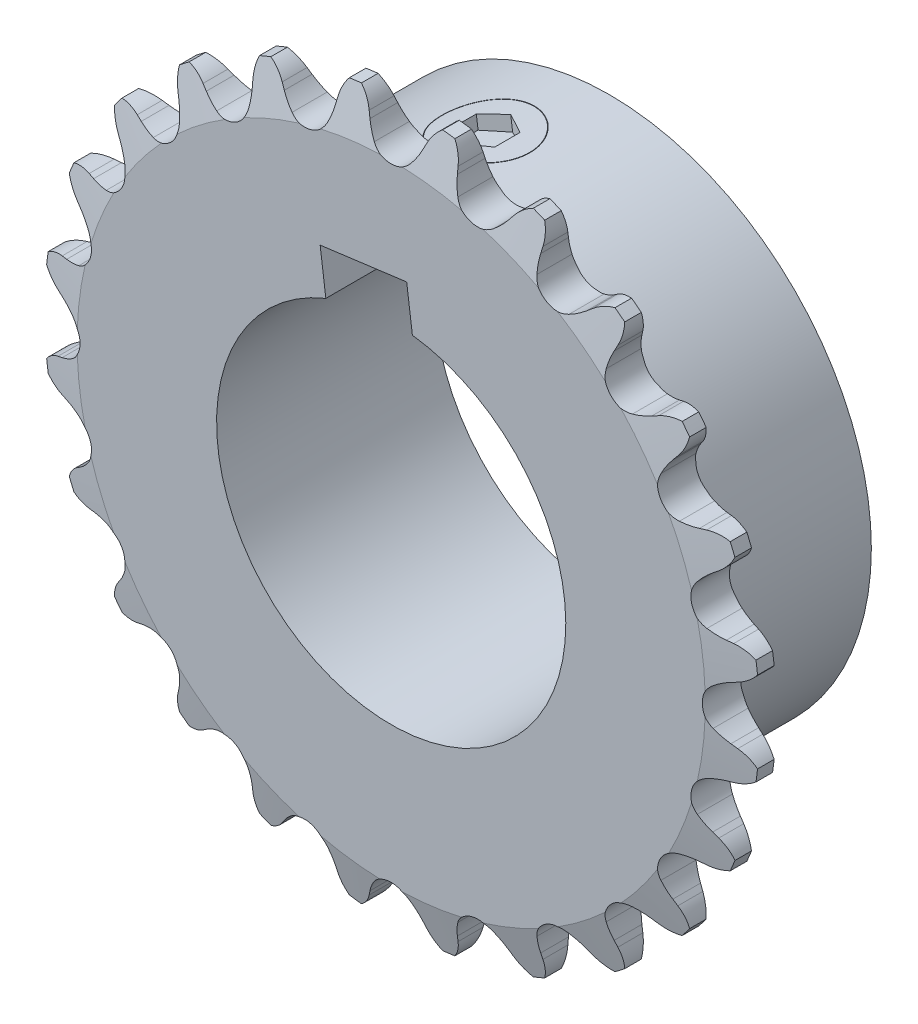
SolidWorks part; units mm, degrees
note: '?' marks a value the reader was unsure of.
ref_plane "Front Plane" through (0, 0, 0) normal (0, 0, 1) x (1, 0, 0)
ref_plane "Top Plane" through (0, 0, 0) normal (0, 1, 0) x (1, 0, 0)
ref_plane "Right Plane" through (0, 0, 0) normal (1, 0, 0) x (0, 0, -1)
ref_axis "Axis1" through (0, 0, -88.99) along (0, 0, 1)?
sketch "Sprocket-BaseSketch" plane through (0, 0, 0) normal (1, 0, 0) x (0, 0, -1)
  line L0 (1.397, 0) -> (1.397, 22.8465)
  line L1 (1.397, 22.8465) -> (0.6032, 26.0215)
  line L2 (0.6032, 26.0215) -> (-0.6032, 26.0215)
  line L3 (-0.6032, 26.0215) -> (-1.397, 22.8465)
  line L4 (-1.397, 22.8465) -> (-1.397, 0)
  line L5 (-1.397, 0) -> (1.397, 0)
  line L6 (5.588, 0) -> (-1.7463, 0) construction
  dimension "Hub Surface" = 1.397
  dimension "RightSide (1)" = 0.7938
  dimension "RightSide (2)" = 3.175
  dimension "OD" = 26.0215
  dimension "LeftSide (1)" = 0.7938
  dimension "LeftSide (2)" = 3.175
  dimension "Tooth Width" = 2.794
revolve "25 (04C) ANSI (ISO) Chain Number, 1.915in P.D." add sketch "Sprocket-BaseSketch" angle 360 about L6
sketch "Tooth-Sketch" plane through (0, 0, 0) normal (0, 0, 1) x (1, 0, 0)
  line L0 (0, 0) -> (0, 32.4328) construction
  line L1 (1.932, 24.319) -> (2.0923, 24.7192)
  line L2 (-1.932, 24.319) -> (-2.0923, 24.7192)
  line L3 (0, 24.3246) -> (6.2957, 23.4958) construction
  line L4 (0, 24.3246) -> (-6.2957, 23.4958) construction
  arc A0 (-1.3466, 23.2913) -> (1.3466, 23.2913) centre (0, 24.3246) ccw
  arc A1 (1.3466, 23.2913) -> (1.932, 24.319) centre (-2.0957, 25.9327) ccw
  arc A2 (-1.3466, 23.2913) -> (-1.932, 24.319) centre (2.0957, 25.9327) cw
  arc A3 (2.0923, 24.7192) -> (4.5833, 26.4046) centre (4.5833, 23.7212) cw
  arc A4 (-2.0923, 24.7192) -> (-4.5833, 26.4046) centre (-4.5833, 23.7212) ccw
  arc A5 (4.5833, 26.4046) -> (-4.5833, 26.4046) centre (0, 0) ccw
extrude "Tooth-Cut, Number of teeth: 24" cut sketch "Tooth-Sketch" against normal through all and the other way through all
pattern_circular "Tooth Pattern, 24 / 24" count 24 every 15 about axis through (0, 0, 0) along (0, 0, 1) of "Tooth-Cut, Number of teeth: 24"
sketch "Sketch3" plane through (0, 0, 0) normal (1, 0, 0) x (0, 0, -1)
  line L0 (-13.081, 0) -> (13.081, 0) construction
  line L1 (1.397, 0) -> (1.397, 19.05)
  line L2 (1.397, 19.05) -> (14.478, 19.05)
  line L3 (14.478, 19.05) -> (14.478, 0)
  line L4 (14.478, 0) -> (1.397, 0)
  dimension "Hub Mounting" = 1.397
  dimension "Hub OD" = 19.05
  dimension "Hub Width" = 13.081
revolve "Hub-Revolve1" add sketch "Sketch3" angle 360 about L0
sketch "Sketch4" plane through (0, 0, -14.478) normal (0, 0, -1) x (-1, 0, 0)
  circle A0 centre (0, 0) radius 12.7
  dimension "Bore Diameter " = 25.4
extrude "Cut-Extrude1" cut sketch "Sketch4" against normal through all
sketch "Sketch5" plane through (0, 0, 0) normal (1, 0, 0) x (0, 0, -1)
  line L0 (14.478, 0) -> (-1.397, 0) construction
  line L1 (14.478, -19.05) -> (14.478, 19.05) construction
  line L2 (-1.397, 0.8085) -> (-1.397, -0.8085) construction
ref_plane "Plane1" through (0, 0, 0) normal (-0.1305, 0.9914, 0) x (-0.9914, -0.1305, 0)
sketch "Sketch6" plane through (0, 0, -14.478) normal (0, 0, -1) x (-1, 0, 0)
  line L0 (-1.5428, 12.6059) -> (-1.1284, 15.7538)
  line L1 (-1.1284, 15.7538) -> (5.1673, 14.9249)
  line L2 (5.1673, 14.9249) -> (4.7529, 11.7771)
  line L3 (4.7529, 11.7771) -> (-1.5428, 12.6059)
  line L4 (8.6566, -1.1397) -> (-8.6566, 1.1397) construction
  circle A0 centre (0, 0) radius 12.7 construction
  dimension "Keyway Wd " = 6.35
  dimension "Keyway Dp " = 3.175
extrude "Cut-Extrude2" cut sketch "Sketch6" against normal through all
sketch "Sketch7" plane through (-2.0195, 15.3394, 0) normal (0.1305, -0.9914, 0) x (0.9914, 0.1305, 0)
  line L0 (0, -14.478) -> (0, -1.397) construction
  line L1 (-2.1786, -1.397) -> (2.1786, -1.397) construction
  line L2 (-3.175, 1.397) -> (-3.175, -14.478) construction
  circle A0 centre (0, -7.9375) radius 3.175
extrude "Cut-Extrude3" cut sketch "Sketch7" against normal through all draft 1 draft outward yes
sketch "Sketch8" plane through (-2.0195, 15.3394, 0) normal (0.1305, -0.9914, 0) x (0.9914, 0.1305, 0)
  line L0 (-3.175, -7.9375) -> (-3.2326, -7.9375) construction
  line L1 (-3.175, 1.397) -> (-3.175, -14.478) construction
  line L2 (-3.2038, -7.9375) -> (-3.2038, -14.478) construction
  line L3 (-19.05, -14.478) -> (19.05, -14.478) construction
  circle A0 centre (0, -7.9375) radius 3.2038
  arc A1 (-3.175, -7.9375) -> (3.175, -7.9375) centre (0, -7.9375) ccw construction
  spline S0 degree 3 poles (-2.797, -9.5747) (-2.5581, -9.9284) (-2.4233, -10.0905) (-2.1245, -10.3867) (-1.9584, -10.522) (-1.6051, -10.7557) (-1.419, -10.8541) (-1.0278, -11.0143) (-0.8212, -11.0759) (-0.4063, -11.1563) (-0.1961, -11.176) (0.23, -11.1738) (0.4428, -11.1514) (0.8561, -11.0665) (1.06, -11.0034) (1.4521, -10.8378) (1.6372, -10.737) (1.9863, -10.5004) (2.1516, -10.3629) (2.4479, -10.0625) (2.5804, -9.8991) (2.8137, -9.5454) (2.9136, -9.3558) (3.0726, -8.9655) (3.1331, -8.7629) (3.2143, -8.3428) (3.2337, -8.1321) (3.2315, -7.7099) (3.2094, -7.4959) (3.1244, -7.08) (3.0621, -6.8785) (2.8984, -6.4883) (2.7961, -6.2991) (2.5603, -5.9498) (2.4262, -5.7875) (2.1243, -5.4879) (1.9595, -5.354) (1.6087, -5.1215) (1.4201, -5.0214) (1.0266, -4.8603) (0.8245, -4.8) (0.4097, -4.7192) (0.1948, -4.699) (-0.2287, -4.7012) (-0.4387, -4.7229) (-0.855, -4.8081) (-1.0599, -4.8717) (-1.4484, -5.0355) (-1.6349, -5.1365) (-1.9876, -5.3754) (-2.1495, -5.5102) (-2.4455, -5.8097) (-2.5808, -5.9765) (-2.8136, -6.3294) (-2.9119, -6.5156) (-3.0719, -6.9074) (-3.1334, -7.1139) (-3.2136, -7.5284) (-3.2336, -7.7388) (-3.2316, -8.1658) (-3.2096, -8.3776) (-3.1254, -8.7911) (-3.0625, -8.9956) (-2.8978, -9.3881) (-2.797, -9.5747) (-2.5581, -9.9284) (-2.4233, -10.0905) knots -0.03125 -0.03125 0 0 0.03125 0.03125 0.0625 0.0625 0.09375 0.09375 0.125 0.125 0.15625 0.15625 0.1875 0.1875 0.21875 0.21875 0.25 0.25 0.28125 0.28125 0.3125 0.3125 0.34375 0.34375 0.375 0.375 0.40625 0.40625 0.4375 0.4375 0.46875 0.46875 0.5 0.5 0.53125 0.53125 0.5625 0.5625 0.59375 0.59375 0.625 0.625 0.65625 0.65625 0.6875 0.6875 0.71875 0.71875 0.75 0.75 0.78125 0.78125 0.8125 0.8125 0.84375 0.84375 0.875 0.875 0.90625 0.90625 0.9375 0.9375 0.96875 0.96875 1 1 1.03125 1.03125 1.0625 only from (-2.6775, -9.7515) to (-2.6775, -9.7515) construction
extrude "Extrude1" add sketch "Sketch8" against normal up to surface (3.3069 mm away)
sketch "Sketch9" plane through (-2.0195, 15.3394, 0) normal (0.1305, -0.9914, 0) x (0.9914, 0.1305, 0)
  line L0 (0, -7.9375) -> (3.2038, -7.9375) construction
  line L1 (1.6019, -7.9375) -> (1.6019, -10.7121) construction
  line L3 (0, -9.7872) -> (1.6019, -8.8624)
  line L4 (1.6019, -8.8624) -> (1.6019, -7.0126)
  line L5 (1.6019, -7.0126) -> (0, -6.0878)
  line L6 (0, -6.0878) -> (-1.6019, -7.0126)
  line L7 (-1.6019, -7.0126) -> (-1.6019, -8.8624)
  line L8 (-1.6019, -8.8624) -> (0, -9.7872)
  circle A0 centre (0, -7.9375) radius 3.2038 construction
  circle A1 centre (0, -7.9375) radius 1.6019 construction
extrude "Cut-Extrude4" cut sketch "Sketch9" against normal through all from offset 2.54
sketch "Sketch10" plane through (0, 0, -14.478) normal (0, 0, -1) x (-1, 0, 0)
  line L0 (-25.7989, 3.3965) -> (25.7989, -3.3965)
  line L1 (-6.2957, -23.4958) -> (0, -24.3246)
  line L2 (8.6566, -1.1397) -> (-8.6566, 1.1397) construction
  line L3 (-26.0277, 1.6589) -> (25.5701, -5.1341)
  line L4 (-6.0669, -21.7582) -> (0.2288, -22.587)
  circle A0 centre (0, 0) radius 26.0215
  circle A1 centre (0, 0) radius 12.7
  arc A2 (-1.5428, 12.6059) -> (4.7529, 11.7771) centre (0, 0) ccw construction
  arc A3 (20.9127, 15.4848) -> (20.3698, 16.1923) centre (0, 0) ccw construction
  dimension "D1" = 1.7526
  dimension "D2" = 1.7526
equation "\"D1@Sketch10\" = \"D2@Sketch10\""
